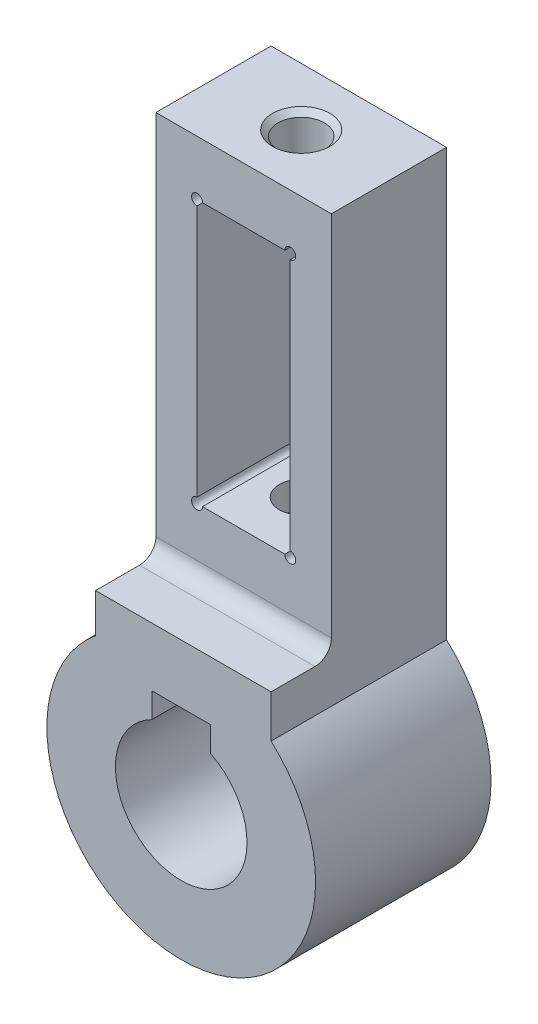
SolidWorks part; units mm, degrees
ref_plane "Front Plane" through (0, 0, 0) normal (0, 0, 1) x (1, 0, 0)
ref_plane "Top Plane" through (0, 0, 0) normal (0, 1, 0) x (1, 0, 0)
ref_plane "Right Plane" through (0, 0, 0) normal (1, 0, 0) x (0, 0, -1)
sketch "Sketch1" plane through (0, 0, 0) normal (0, 0, 1) x (1, 0, 0)
  line L0 (0, 24) -> (0, -24) construction
  line L5 (-16, 34) -> (16, 34)
  line L6 (-16, 34) -> (-16, -36)
  line L7 (-8.5, 24) -> (8.5, 24)
  line L8 (-8.5, 24) -> (-8.5, -24)
  line L9 (-8.5, -24) -> (8.5, -24)
  line L10 (8.5, 24) -> (8.5, -24)
  line L11 (-8.5, 24) -> (8.5, -24) construction
  line L12 (-8.5, -24) -> (8.5, 24) construction
  line L13 (-16, -36) -> (16, -36)
  line L14 (16, 34) -> (16, -36)
  line L18 (-8.5, 0) -> (8.5, 0) construction
  circle A0 centre (-8.5, 24) radius 1
  circle A1 centre (8.5, 24) radius 1
  circle A2 centre (-8.5, -24) radius 1
  circle A3 centre (8.5, -24) radius 1
  point P0 (0, 0)
  point P1 (0, 0)
  point P7 (0, 0)
  dimension "D3" = 2
  dimension "D1" = 48
  dimension "D2" = 17
  dimension "D4" = 32
  dimension "D5" = 10
  dimension "D6" = 70
extrude "Boss-Extrude1" add sketch "Sketch1" along normal blind 21 contours L14 L5 L6 L13 A3 L9 A2 L8 A0 L7 A1 L10 region at (0, 33.2303, 0)
sketch "Sketch3" plane through (0, 0, 0) normal (0, 0, 1) x (1, 0, 0)
  line L1 (-16, -36) -> (16, -36)
  line L2 (-16, -36) -> (-16, -52.8938)
  line L3 (-16, -52.8938) -> (16, -52.8938)
  line L4 (16, -36) -> (16, -52.8938)
  line L5 (-16, -36) -> (16, -36) construction
  line L6 (-5.7574, -51.2703) -> (4.9894, -51.2703)
  line L7 (-5.7574, -51.2703) -> (-5.7574, -46.7)
  line L8 (-5.7574, -46.7) -> (4.9894, -46.7)
  line L9 (4.9894, -51.2703) -> (4.9894, -46.7)
  line L10 (-16, 34) -> (16, 34) construction
  circle A0 centre (-0.384, -62) radius 24.5
  circle A1 centre (-0.384, -62) radius 12
  point P16 (-0.384, -74)
  dimension "D3" = 49
  dimension "D4" = 24
  dimension "D1" = 32
  dimension "D2" = 26
  dimension "D5" = 27.3
  dimension "D6" = 96
extrude "Boss-Extrude2" add sketch "Sketch3" along normal blind 32 contours A0 L4 L1 L2 | A1 L3 L2 A0 L4 | A1 L3 L4 A0 L2 L7 L8 L9 region at (0, -36.3293, 0) region at (-0.0631, -45.2539, 0) region at (-16.6544, -48.0078, 0)
fillet "Fillet1" radius 3 1 edges at (0, -36, 21)
sketch "Sketch4" plane through (0, 34, 0) normal (0, 1, 0) x (1, 0, 0)
  line L0 (0, 0) -> (0, -21) construction
  line L1 (-16, -21) -> (16, -21) construction
  circle A0 centre (0, -10.5) radius 4.2313
  point P5 (0, -21)
extrude "Cut-Extrude1" cut sketch "Sketch4" against normal blind 32
chamfer "Chamfer1" distance 1 angle 45 1 edges at (0, 34, 14.7313)
hole_wizard "Ø8.0mm Dowel Hole1" positions "3DSketch1" profile "Sketch6" hole size "Ø8.0" standard "ISO"
sketch3d "3DSketch1"
  line L0 (0, -24, 10.5) -> (0, -24, 21) construction
  line L1 (-7.5, -24, 21) -> (7.5, -24, 21) construction
  line L2 (0, -24, 10.5) -> (7.5, -24, 10.5) construction
  line L3 (7.5, -24, 21) -> (7.5, -24, 0) construction
  point P0 (0, -24, 10.5)
sketch "Sketch6" plane through (0, -24, 10.5) normal (1, 0, 0) x (0, 0, 1)
  line L0 (0, 0) -> (0, 7.4034)
  line L1 (0, 7.4034) -> (4, 5)
  line L2 (4, 5) -> (4, 0)
  line L5 (4, 0) -> (0, 0)
  line L10 (0, 7.4034) -> (-4, 5) construction
  line L11 (0, -6.35) -> (0, 107.95) construction
  dimension "Hole Dia." = 8
  dimension "Hole Depth" = 5
  dimension "Drill Angle" = 118
